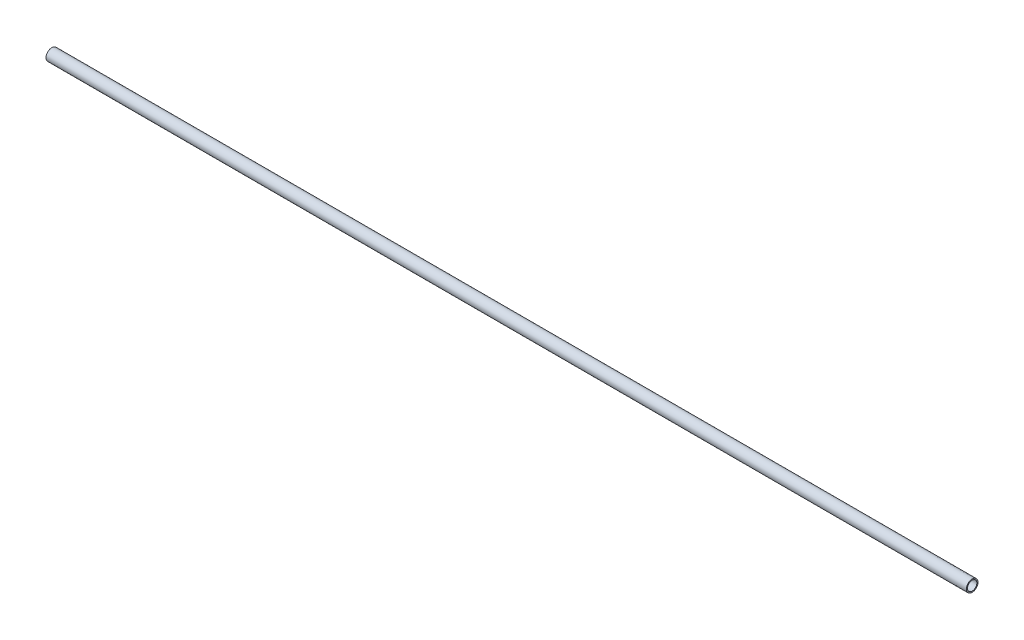
SolidWorks part; units mm, degrees
ref_plane "Front Plane" through (0, 0, 0) normal (0, 0, 1) x (1, 0, 0)
ref_plane "Top Plane" through (0, 0, 0) normal (0, 1, 0) x (1, 0, 0)
ref_plane "Right Plane" through (0, 0, 0) normal (1, 0, 0) x (0, 0, -1)
ref_axis "Axis1" through (-2, 0, 0) along (1, 0, 0)
sketch "Sketch1" plane through (0, 0, 0) normal (1, 0, 0) x (0, 0, -1)
  circle A0 centre (0, 0) radius 0.2032
  circle A1 centre (0, 0) radius 0.254
  dimension "D1" = 0.4064
  dimension "D2" = 0.508
extrude "Boss-Extrude1" add sketch "Sketch1" along normal blind 40
equation "\"Do\"=8.5mm"
equation "\"Lo\"=10"
equation "\"screw_diam\" = 3.5mm"
equation "\"wheel_Do\"=12.5mm"
equation "\"wheel_thickness\"=4mm"
equation "\"Collet_diameter\"=4.3"
equation "\"clearance\"= 0.5mm"
equation "\"handle_body_width\" = 10mm"
equation "\"finger_diameter\"=35"
equation "\"collet_lid_diameter\"=10"
equation "\"screw_cap_diam\"=5.15"
equation "\"handle_thickness\"=12.5mm"
equation "\"post_hole_diam\"=2"
equation "\"roll_rod_diam\"= 6.5 "
equation "\"roll_rod_length\"=6.6"
equation "\"disc_diam\"=5"
equation "\"disc_width\"=1.5"
equation "\"arm_width\"=5"
equation "\"arm_thickness\"=4.5"
equation "\"wheel_total_diam\"=30"
equation "\"spring_diam\"=4.1"
equation "\"collet_length\" = 18.75mm"
equation "\"tip_length\" = 40mm"
equation "\"D1@Boss-Extrude1\"=\"tip_length\""
